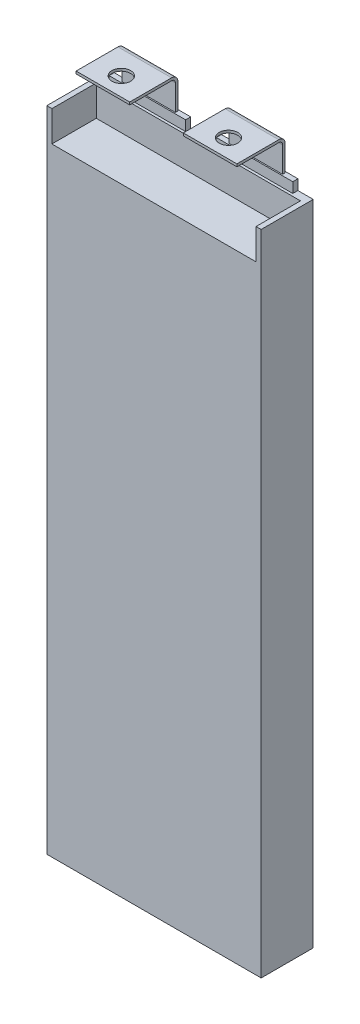
SolidWorks part; units mm, degrees
ref_plane "Front Plane" through (0, 0, 0) normal (0, 0, 1) x (1, 0, 0)
ref_plane "Top Plane" through (0, 0, 0) normal (0, 1, 0) x (1, 0, 0)
ref_plane "Right Plane" through (0, 0, 0) normal (1, 0, 0) x (0, 0, -1)
sketch "Sketch1" plane through (0, 0, 0) normal (0, 0, 1) x (1, 0, 0)
  line L1 (-21, 0) -> (21, 0)
  line L2 (-21, 0) -> (-21, 127)
  line L3 (-21, 127) -> (21, 127)
  line L4 (21, 0) -> (21, 127)
  dimension "D1" = 127
  dimension "D2" = 42
extrude "Boss-Extrude1" add sketch "Sketch1" along normal mid plane 10.2
ref_plane "Tab Mid Plane" through (0, 0, -4.6) normal (0, 0, -1) x (-1, 0, 0)
sketch "Sketch2" plane through (0, 0, 5.1) normal (0, 0, 1) x (1, 0, 0)
  line L0 (21, 127) -> (-21, 127) construction
  line L1 (-20, 127) -> (20, 127)
  line L2 (-20, 127) -> (-20, 121)
  line L3 (-20, 121) -> (20, 121)
  line L4 (20, 127) -> (20, 121)
  line L5 (-21, 127) -> (-21, 0) construction
  point P8 (0, 127)
  dimension "D1" = 1
  dimension "D2" = 6
extrude "Cut-Extrude1" cut sketch "Sketch2" against normal offset from surface (8.7 mm away) 1 up to plane "Tab Mid Plane"
sketch "Sketch3" plane through (0, 0, -4.6) normal (0, 0, -1) x (-1, 0, 0)
  line L0 (-21, 127) -> (21, 127) construction
  line L1 (-18, 127) -> (-3, 127)
  line L2 (-18, 127) -> (-18, 129)
  line L3 (-18, 129) -> (-3, 129)
  line L4 (-3, 127) -> (-3, 129)
  line L5 (-3, 127) -> (3, 127) construction
  line L6 (3, 127) -> (18, 127)
  line L7 (3, 127) -> (3, 129)
  line L8 (3, 129) -> (18, 129)
  line L9 (18, 127) -> (18, 129)
  point P10 (-10.5, 129)
  point P11 (10.5, 129)
  point P12 (0, 127)
  dimension "D1" = 21
  dimension "D2" = 2
  dimension "D3" = 15
extrude "Boss-Extrude2" add sketch "Sketch3" along normal mid plane 1
sketch "Tab Profile" plane through (0, 129, 0) normal (0, 1, 0) x (1, 0, 0)
  line L0 (-18, 5.1) -> (-3, 4.1) construction
  line L1 (-15.75, 4.85) -> (-5.25, 4.85)
  line L2 (-15.75, 4.85) -> (-15.75, 4.35)
  line L3 (-15.75, 4.35) -> (-5.25, 4.35)
  line L4 (-5.25, 4.85) -> (-5.25, 4.35)
  line L5 (5.25, 4.85) -> (15.75, 4.85)
  line L6 (5.25, 4.85) -> (5.25, 4.35)
  line L7 (5.25, 4.35) -> (15.75, 4.35)
  line L8 (15.75, 4.85) -> (15.75, 4.35)
  line L9 (3, 5.1) -> (18, 4.1) construction
  line L10 (-15.75, 4.35) -> (-5.25, 4.85) construction
  line L11 (5.25, 4.35) -> (15.75, 4.85) construction
  point P16 (-10.5, 4.6)
  point P17 (10.5, 4.6)
  dimension "D1" = 10.5
  dimension "D2" = 0.5
sketch "Tab Bend" plane through (0, 0, 0) normal (1, 0, 0) x (0, 0, -1)
  line L0 (4.6, 129) -> (4.6, 135)
  line L1 (5.1, 129) -> (4.1, 129) construction
  line L2 (4.6, 135) -> (-4.6, 135)
  line L3 (4.6, 129) -> (-6.6, 129) construction
  point P1 (-1, 129)
  dimension "D2" = 11.2
  dimension "D1" = 6
  dimension "D3" = 3.6
sweep "Tabs" add profiles "Tab Profile" path "Tab Bend"
fillet "Fillet2" radius 0.75 1 edges at (10.5, 134.75, -4.35) type face fillet first side face at (10.5, 131.875, -4.35) second side face at (10.5, 134.75, 0.125)
fillet "Fillet1" radius 1.25 1 edges at (10.5, 135.25, -4.85) type face fillet first side face at (10.5, 132.125, -4.85) second side face at (10.5, 135.25, -0.125)
fillet "Fillet4" radius 0.75 1 edges at (-10.5, 134.75, -4.35) type face fillet first side face at (-10.5, 131.875, -4.35) second side face at (-10.5, 134.75, 0.125)
fillet "Fillet3" radius 1.25 1 edges at (-10.5, 135.25, -4.85) type face fillet first side face at (-10.5, 132.125, -4.85) second side face at (-10.5, 135.25, -0.125)
hole_wizard "#6 Clearance Hole1" positions "Sketch9" profile "Sketch10" hole size "#6" standard "ANSI Inch" end condition up to next
sketch "Sketch9" plane through (0, 135.25, 0) normal (0, 1, 0) x (1, 0, 0)
  line L0 (-15.75, 2.6) -> (-5.25, -4.6) construction
  line L4 (-15.75, 3.6) -> (-15.75, -4.6) construction
  point P0 (-10.5, -1)
  dimension "D1" = 7.2
sketch "Sketch10" plane through (-10.5, 135.25, 1) normal (1, 0, 0) x (0, 0, 1)
  line L0 (0, 0) -> (0, 0.5)
  line L1 (0, 0.5) -> (1.8288, 0.5)
  line L2 (1.8288, 0.5) -> (1.8288, 0)
  line L5 (1.8288, 0) -> (0, 0)
  line L11 (0, -6.35) -> (0, 107.95) construction
  dimension "Thru Hole Dia." = 3.6576
  dimension "Thru Hole Depth" = 0.5
hole_wizard "#6 Clearance Hole2" positions "Sketch11" profile "Sketch12" hole size "#6" standard "ANSI Inch" end condition up to next
sketch "Sketch11" plane through (0, 135.25, 0) normal (0, 1, 0) x (1, 0, 0)
  line L0 (5.25, 2.6) -> (15.75, -4.6) construction
  line L1 (5.25, 3.6) -> (5.25, -4.6) construction
  point P0 (10.5, -1)
  dimension "D1" = 7.2
sketch "Sketch12" plane through (10.5, 135.25, 1) normal (1, 0, 0) x (0, 0, 1)
  line L0 (0, 0) -> (0, 0.5)
  line L1 (0, 0.5) -> (1.8288, 0.5)
  line L2 (1.8288, 0.5) -> (1.8288, 0)
  line L5 (1.8288, 0) -> (0, 0)
  line L11 (0, -6.35) -> (0, 107.95) construction
  dimension "Thru Hole Dia." = 3.6576
  dimension "Thru Hole Depth" = 0.5
split "Split1" [suppressed] bodies to split 108
mirror "Mirror3" [suppressed] about plane through (0, 0, -4.6) normal (0, 0, -1) of bodies 110 109
delete or keep bodies "Body-Delete/Keep 1" [suppressed] type delete bodies bodies 110 109
